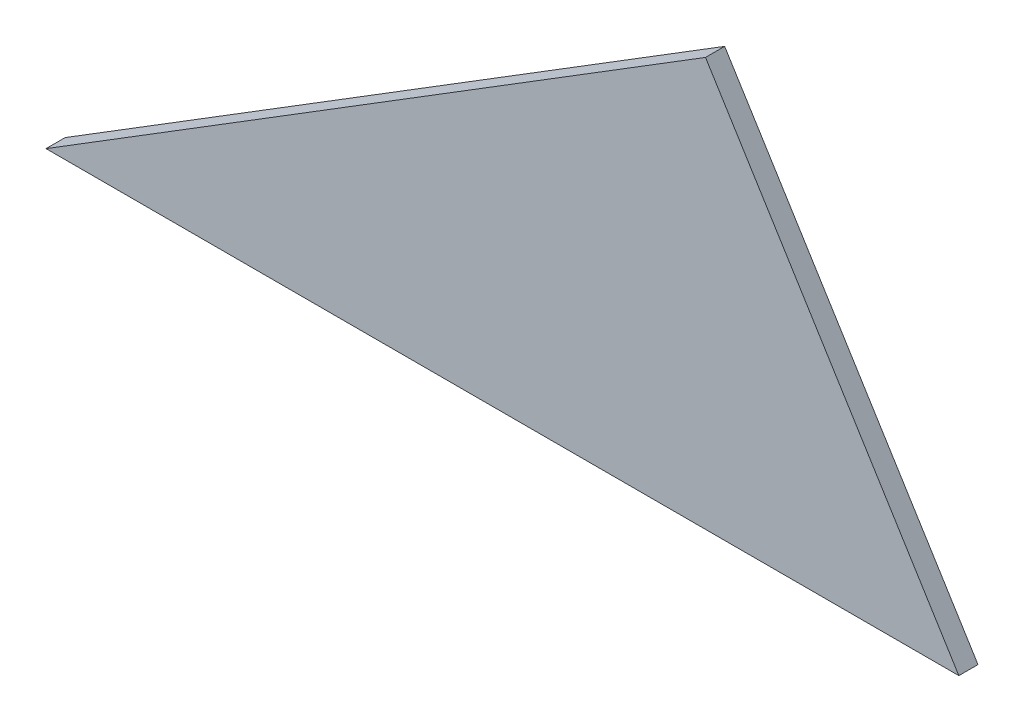
SolidWorks part; units mm, degrees
ref_plane "Front Plane" through (0, 0, 0) normal (0, 0, 1) x (1, 0, 0)
ref_plane "Top Plane" through (0, 0, 0) normal (0, 1, 0) x (1, 0, 0)
ref_plane "Right Plane" through (0, 0, 0) normal (1, 0, 0) x (0, 0, -1)
sketch "Sketch1" plane through (0, 0, 0) normal (0, 0, 1) x (1, 0, 0)
  line L0 (0, 0) -> (68.8544, 42.6744)
  line L1 (68.8544, 42.6744) -> (95.303, 0)
  line L2 (95.303, 0) -> (0, 0)
base flange "Base-Flange1" sketch "Sketch1" thickness 2 reverse thickness direction no parameters "D1"=0.7366
sketch "Bend-Lines1" [suppressed] plane through (0, 0, 0) normal (0, 1, 0) x (1, 0, 0)
sketch "Bounding-Box1" [suppressed] plane through (0, 0, 0) normal (0, 1, 0) x (1, 0, 0)
sheet metal parameters "Sheet-Metal1" thickness 2 parameters "D1"=0.7366
flat pattern "Flat-Pattern1" [suppressed]
sketch "Bend-Lines2" plane through (0, 0, 0) normal (0, 1, 0) x (1, 0, 0)
sketch3d "Bounding-Box2" [suppressed]
  line L0 (0, 0, 0) -> (-95.303, 0, 0) construction
  line L1 (0, 42.6744, 0) -> (-95.303, 42.6744, 0) construction
  line L2 (0, 0, 0) -> (0, 42.6744, 0) construction
  line L3 (-95.303, 0, 0) -> (-95.303, 42.6744, 0) construction
